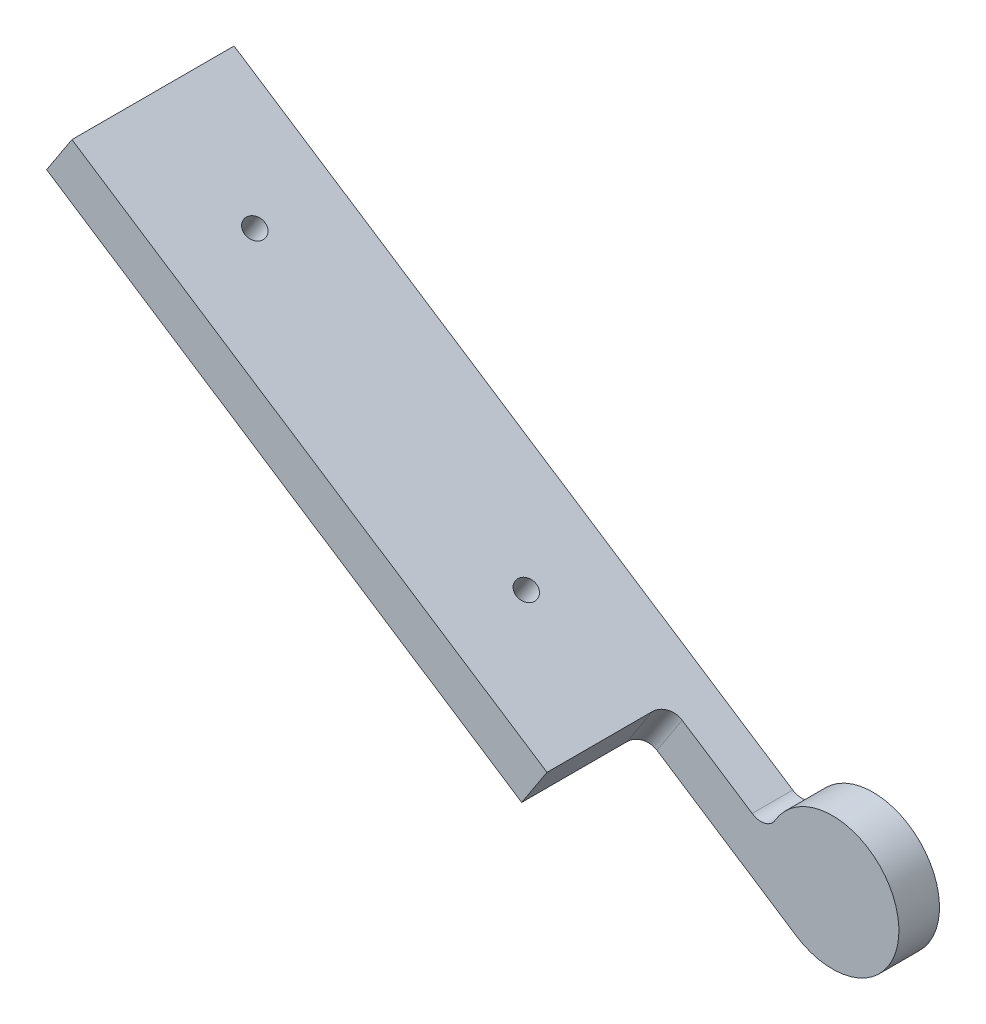
SolidWorks part; units mm, degrees
ref_plane "Front Plane" through (0, 0, 0) normal (0, 0, 1) x (1, 0, 0)
ref_plane "Top Plane" through (0, 0, 0) normal (0, 1, 0) x (1, 0, 0)
ref_plane "Right Plane" through (0, 0, 0) normal (1, 0, 0) x (0, 0, -1)
sketch "Sketch1" plane through (0, 0, 0) normal (0, 0, 1) x (1, 0, 0)
  circle A0 centre (0, 0) radius 10.414
extrude "Boss-Extrude1" add sketch "Sketch1" along normal blind 6.35
sketch "Sketch2" plane through (0, 0, 6.35) normal (0, 0, 1) x (1, 0, 0)
  line L0 (-10.0398, 2.7667) -> (-100.083, 61.5943)
  line L3 (-100.083, 61.5943) -> (-25.6587, 12.9709) construction
  line L4 (-100.083, 61.5943) -> (-104.0423, 55.534)
  line L5 (-104.0423, 55.534) -> (-5.6959, -8.7183)
  circle A0 centre (0, 0) radius 10.414 construction
  arc A1 (-10.0398, 2.7667) -> (-5.6959, -8.7183) centre (0, 0) ccw
extrude "Boss-Extrude2" add sketch "Sketch2" against normal up to surface (6.35 mm away) up to face at (10.414, 0, 0)
sketch "Sketch3" plane through (-5.6959, -8.7183, 0) normal (-0.5469, -0.8372, 0) x (-0.8372, 0.5469, 0)
  line L0 (28.575, 44.8691) -> (28.575, -412.3309) construction
  line L1 (117.475, 0) -> (28.575, 0)
  line L2 (117.475, 0) -> (117.475, -25.4)
  line L3 (117.475, -25.4) -> (28.575, -25.4)
  line L4 (28.575, 0) -> (28.575, -25.4)
  dimension "D1" = 25.4
extrude "Boss-Extrude3" add sketch "Sketch3" against normal up to surface (7.239 mm away)
fillet "Fillet1" radius 2.54 2 edges at (-10.0398, 2.7667, 3.175) (-27.6383, 9.9408, 6.35)
sketch "Sketch4" plane through (-5.6959, -8.7183, 0) normal (-0.5469, -0.8372, 0) x (-0.8372, 0.5469, 0)
  line L0 (151.4222, -12.7) -> (-39.6458, -12.7) construction
  line L1 (0, 0) -> (117.475, 0) construction
  line L2 (28.575, -25.4) -> (117.475, -25.4) construction
  line L3 (73.025, 14.4099) -> (73.025, -43.6142) construction
  line L4 (28.575, -8.89) -> (28.575, -25.4) construction
  line L5 (117.475, 0) -> (117.475, -25.4) construction
  circle A0 centre (47.625, -12.7) radius 1.5875
  circle A1 centre (98.425, -12.7) radius 1.5875
  dimension "D1" = 3.175
  dimension "D2" = 50.8
extrude "Cut-Extrude1" cut sketch "Sketch4" against normal through all
